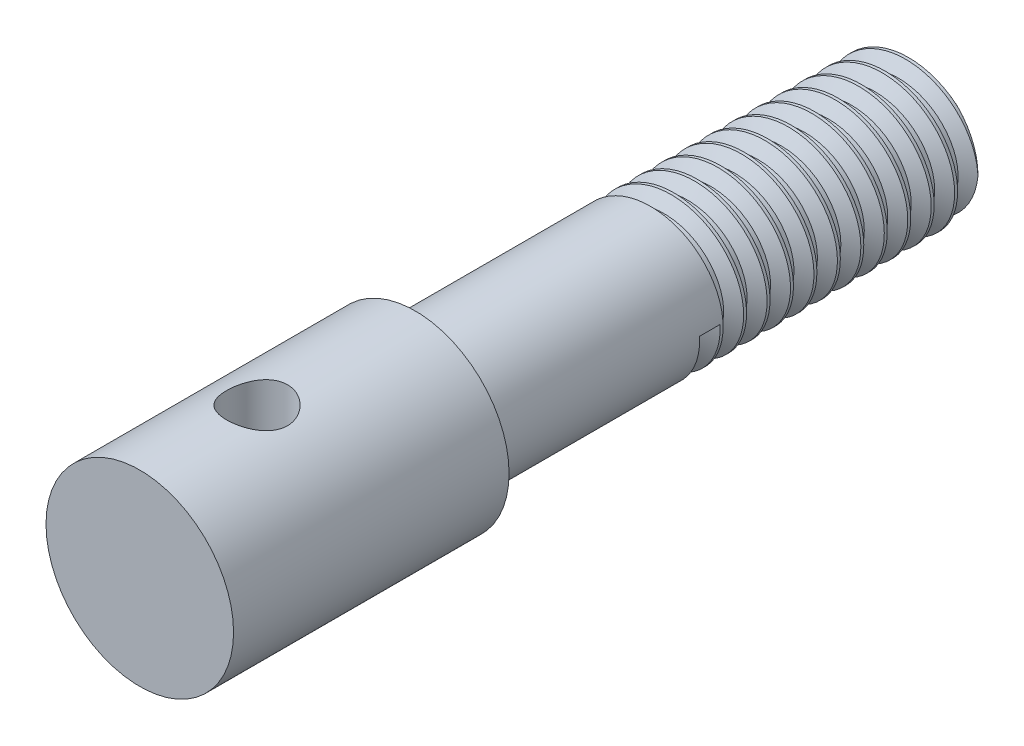
SolidWorks part; units mm, degrees
ref_plane "Alzado" through (0, 0, 0) normal (0, 0, 1) x (1, 0, 0)
ref_plane "Planta" through (0, 0, 0) normal (0, 1, 0) x (1, 0, 0)
ref_plane "Vista lateral" through (0, 0, 0) normal (1, 0, 0) x (0, 0, -1)
sketch "Croquis1" plane through (0, 0, 0) normal (0, 0, 1) x (1, 0, 0)
  circle A0 centre (0, 0) radius 4
  dimension "D1" = 8
extrude "Saliente-Extruir1" add sketch "Croquis1" along normal blind 36.75
ref_plane "Plano1" through (0, 4, 0) normal (0, 1, 0) x (1, 0, 0)
sketch "Croquis2" plane through (0, 4, 0) normal (0, 1, 0) x (1, 0, 0)
  line L0 (-4, -36.75) -> (4, -36.75) construction
  line L1 (-4, 0) -> (-4, -36.75) construction
  circle A0 centre (0, -31.75) radius 1.3
  dimension "D1" = 2.6
  dimension "D2" = 5
  dimension "D3" = 4
extrude "Cortar-Extruir1" cut sketch "Croquis2" against normal through all
sketch "Croquis3" plane through (0, 0, 0) normal (0, 0, -1) x (-1, 0, 0)
  circle A0 centre (0, 0) radius 3
  circle A2 centre (0, 0) radius 4
  dimension "D1" = 6
  dimension "D2" = 8
extrude "Cortar-Extruir2" cut sketch "Croquis3" against normal blind 25
thread "Rosca1" pitch 1 method cut profile "Perfil de rosca1" start angle 0, offset 0, length 15, pitch 1, diameter 6
ref_plane "Plano2" through (3, 0, 0) normal (0, -1, 0) x (1, 0, 0)
sketch "Perfil de rosca1" plane through (3, 0, 0) normal (0, -1, 0) x (1, 0, 0)
  line L0 (0, 0) -> (0, 1) construction
  line L11 (0, 0) -> (0, 0.875)
  line L12 (0, 0.875) -> (-0.5413, 0.5625)
  line L13 (-0.5413, 0.5625) -> (-0.5413, 0.3125)
  line L15 (-0.5413, 0.3125) -> (0, 0)
  line L17 (-0.5413, 0.4375) -> (0, 0.4375) construction
  point P2 (0, 0)
  dimension "Pitch" = 1
  dimension "Profile_Angle" = 60
  dimension "Profile_Land" = 0.25
  dimension "Profile_Height" = 0.5413
ref_plane "Plano3" through (0, 4, 0) normal (0, 1, 0) x (1, 0, 0)
sketch "Croquis8" plane through (0, 4, 0) normal (0, 1, 0) x (1, 0, 0)
  line L0 (-10, 0) -> (10, 0)
  line L1 (-10, 0) -> (-10, -4)
  line L2 (-10, -4) -> (10, -4)
  line L3 (10, -4) -> (10, 0)
  line L4 (3, 0) -> (-3, 0) construction
  line L5 (0, 0) -> (0, 3.2967) construction
  dimension "D1" = 4
  dimension "D2" = 20
extrude "Cortar-Extruir3" cut sketch "Croquis8" against normal through all
